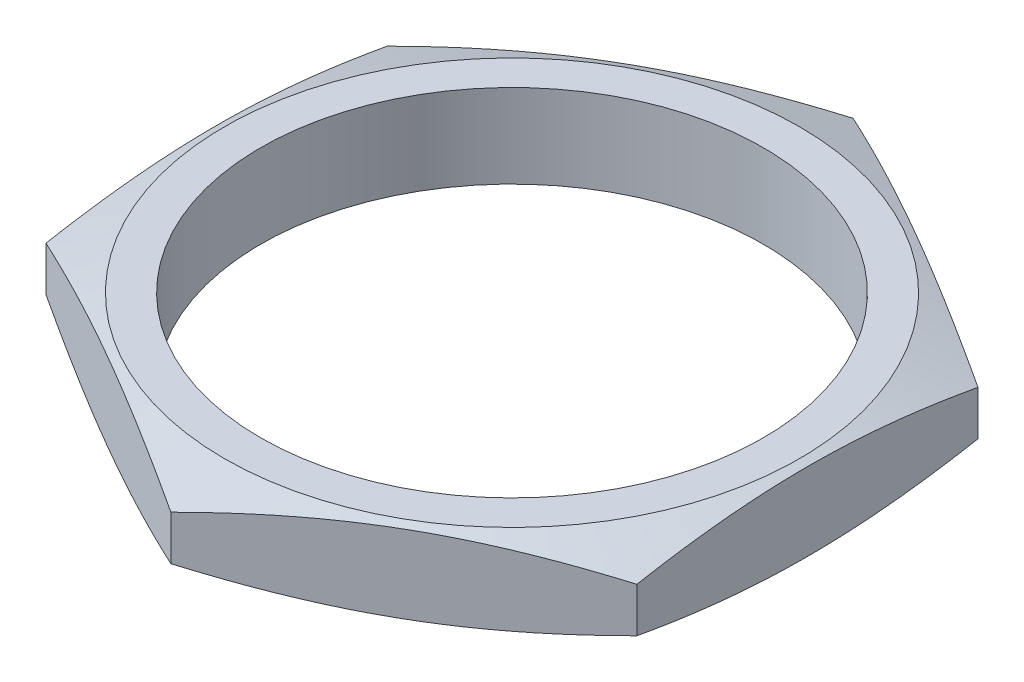
SolidWorks part; units mm, degrees
material "Plain Carbon Steel"
ref_plane "Front Plane" through (0, 0, 0) normal (0, 0, 1) x (1, 0, 0)
ref_plane "Top Plane" through (0, 0, 0) normal (0, 1, 0) x (1, 0, 0)
ref_plane "Right Plane" through (0, 0, 0) normal (1, 0, 0) x (0, 0, -1)
sketch "Sketch1" plane through (0, 0, 0) normal (0, 1, 0) x (1, 0, 0)
  line L0 (0, -1.0897) -> (0, 1.0897) construction
  line L1 (0, -8.0802) -> (6.9977, -4.0401)
  line L2 (6.9977, -4.0401) -> (6.9977, 4.0401)
  line L3 (6.9977, 4.0401) -> (0, 8.0802)
  line L4 (0, 8.0802) -> (-6.9977, 4.0401)
  line L5 (-6.9977, 4.0401) -> (-6.9977, -4.0401)
  line L6 (-6.9977, -4.0401) -> (0, -8.0802)
  circle A0 centre (0, 0) radius 5.9531
  circle A1 centre (0, 0) radius 6.9977 construction
  dimension "D1" = 11.9062
  dimension "D2" = 13.9954
extrude "Boss-Extrude1" add sketch "Sketch1" along normal blind 1.9812
sketch "Sketch2" plane through (0, 0, 0) normal (1, 0, 0) x (0, 0, -1)
  line L0 (-8.0802, 1.519) -> (-6.8102, 1.9812)
  line L1 (-8.0802, 1.9812) -> (-8.0802, 0) construction
  line L2 (-8.0802, 1.9812) -> (-4.0401, 1.9812) construction
  line L3 (-6.8102, 1.9812) -> (-8.0802, 1.9812)
  line L4 (-8.0802, 1.9812) -> (-8.0802, 1.519)
  line L5 (0, 0) -> (0, 1.9812) construction
  line L6 (-4.0401, 1.9812) -> (4.0401, 1.9812) construction
  line L7 (-8.0802, 0.9906) -> (0, 0.9906) construction
  line L8 (-8.0802, 0) -> (-8.0802, 0.4622)
  line L9 (-6.8102, 0) -> (-8.0802, 0)
  line L10 (-8.0802, 0.4622) -> (-6.8102, 0)
  dimension "D1" = 20
  dimension "D2" = 1.27
revolve "Cut-Revolve1" cut sketch "Sketch2" angle 360 about L5
